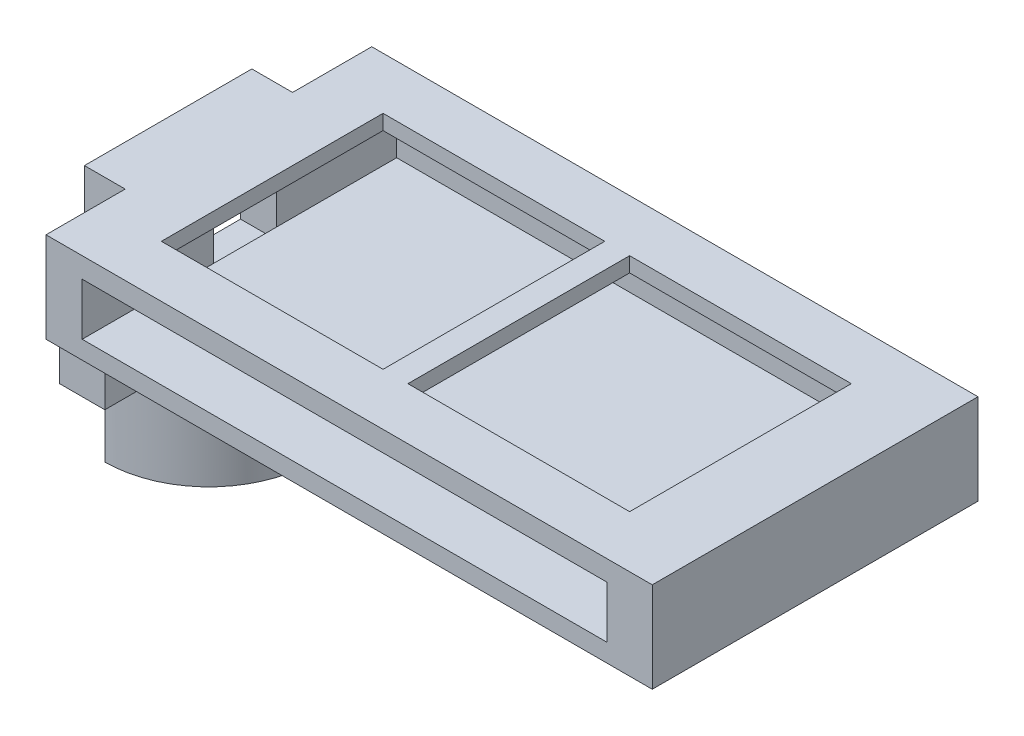
SolidWorks part; units mm, degrees
ref_plane "Front Plane" through (0, 0, 0) normal (0, 0, 1) x (1, 0, 0)
ref_plane "Top Plane" through (0, 0, 0) normal (0, 1, 0) x (1, 0, 0)
ref_plane "Right Plane" through (0, 0, 0) normal (1, 0, 0) x (0, 0, -1)
sketch "Sketch5" plane through (0, 0, 0) normal (0, 1, 0) x (1, 0, 0)
  line L0 (-124, 0) -> (-134, 0)
  line L1 (0, 0) -> (-1.9533, 0)
  line L2 (0, 0) -> (0, 72)
  line L3 (0, 72) -> (-134, 72)
  line L4 (-134, 0) -> (-134, 72)
  line L10 (-124, 0) -> (-1.9533, 0)
  dimension "D1" = 72
  dimension "D2" = 134
extrude "Main Body" add sketch "Sketch5" against normal blind 16 contours L1 L2 L3 L4 region at (-67, 0, -36)
sketch "Sketch8" plane through (0, 0, 0) normal (0, 0, 1) x (1, 0, 0)
  line L0 (-134, -16) -> (-134, 0) construction
  line L1 (0, -16) -> (-134, -16)
  line L2 (0, -16) -> (0, -20)
  line L3 (0, -20) -> (-134, -20)
  line L4 (-134, -16) -> (-134, -20)
  dimension "D1" = 4
extrude "Cover" add sketch "Sketch8" against normal up to surface (72 mm away) up to face at (-67, -8, -72)
sketch "Sketch20" plane through (0, 0, 0) normal (0, 0, 1) x (1, 0, 0)
  line L0 (-134, -20) -> (-134, 0) construction
  line L1 (-10, -4.5) -> (-126, -4.5)
  line L2 (-10, -4.5) -> (-10, -16)
  line L3 (-10, -16) -> (-126, -16)
  line L4 (-126, -4.5) -> (-126, -16)
  line L5 (0, -20) -> (0, 0) construction
  line L7 (-134, -20) -> (0, -20) construction
  dimension "D1" = 8
  dimension "D2" = 10
  dimension "D3" = 11.5
  dimension "D4" = 4
extrude "Crystal Slot" cut sketch "Sketch20" against normal offset from surface (69.5 mm away) 2.5 contours L2 L1 L4 L3 up to face at (-67, -10, -72)
sketch "Sketch9" plane through (-134, 0, 0) normal (-1, 0, 0) x (0, 0, 1)
  line L3 (-29, -4.5) -> (-43, -4.5)
  line L4 (-43, -18.5) -> (-43, -4.5)
  line L5 (-72, -20) -> (-72, 0) construction
  line L6 (-69.5, -4.5) -> (0, -4.5) construction
  line L7 (-29, -4.5) -> (-29, -18.5)
  line L8 (-29, -18.5) -> (-43, -18.5)
  dimension "D1" = 14
  dimension "D2" = 14
  dimension "D3" = 29
  dimension "D4" = 0
extrude "SiPM Window" cut sketch "Sketch9" against normal up to surface (8 mm away) up to face at (-126, -10.25, -34.75)
sketch "Sketch10" plane through (0, -20, 0) normal (0, -1, 0) x (1, 0, 0)
  line L0 (-134, -72) -> (-134, 0) construction
  line L4 (-134, -72) -> (-134, 0) construction
  line L5 (-134, -72) -> (0, -72) construction
  line L6 (-134, -16) -> (-134, -13)
  line L7 (-134, -56) -> (-134, -59)
  arc A0 (-134, -56) -> (-134, -16) centre (-134, -36) ccw
  arc A1 (-134, -59) -> (-134, -13) centre (-134, -36) ccw
  line M4 (-134, 0) -> (-134, -72)
  line M8 (-134, 0) -> (-134, -72)
  dimension "D2" = 20
  dimension "D1" = 36
  dimension "D3" = 3
  dimension "D4" = 3
extrude "Tube Adapter" add sketch "Sketch10" along normal blind 30 contours A1 A0 M4 M8 region at (-133.4857, -20, -14.5)
sketch "Sketch11" plane through (0, -20, 0) normal (0, -1, 0) x (1, 0, 0)
  line L0 (-134, -59) -> (-134, -69)
  line L5 (-134, -72) -> (-134, -59) construction
  line L6 (-134, -69) -> (-124, -69)
  line L7 (-124, -69) -> (-124, -56.7123)
  arc A0 (-134, -59) -> (-124, -56.7123) centre (-134, -36) ccw
  dimension "D1" = 10
  dimension "D2" = 10
extrude "Right Screw Terminal" add sketch "Sketch11" along normal blind 10
sketch "Sketch12" plane through (-134, 0, 0) normal (-1, 0, 0) x (0, 0, 1)
  line L2 (-69, -30) -> (-69, -20) construction
  line L3 (-59, -30) -> (-69, -30) construction
  circle A0 centre (-64, -25) radius 1.524
  dimension "D3" = 5
  dimension "D1" = 3.048
  dimension "D2" = 5
extrude "Right Screw Hole" cut sketch "Sketch12" against normal up to next
sketch "Sketch13" plane through (0, -20, 0) normal (0, -1, 0) x (-1, 0, 0)
  line L2 (134, 13) -> (134, 3)
  line L3 (134, 3) -> (124, 3)
  line L4 (124, 15.2877) -> (124, 3)
  arc A0 (134, 13) -> (124, 15.2877) centre (134, 36) cw
  dimension "D1" = 10
  dimension "D2" = 10
extrude "Left Screw Terminal" add sketch "Sketch13" along normal blind 10
sketch "Sketch14" plane through (-134, 0, 0) normal (-1, 0, 0) x (0, 0, 1)
  line L0 (-3, -30) -> (-3, -20) construction
  line L1 (-3, -30) -> (-13, -30) construction
  circle A0 centre (-8, -25) radius 1.524
  dimension "D3" = 3.048
  dimension "D1" = 5
  dimension "D2" = 5
extrude "Left Screw Hole" cut sketch "Sketch14" against normal up to next
sketch "Sketch15" plane through (-134, 0, 0) normal (-1, 0, 0) x (0, 0, 1)
  line L0 (-56, -20) -> (-16, -20) construction
  line L1 (-17.5, -20) -> (-54.5, -20)
  line L2 (-17.5, -20) -> (-17.5, 0)
  line L3 (-17.5, 0) -> (-54.5, 0)
  line L4 (-54.5, -20) -> (-54.5, 0)
  line L7 (0, 0) -> (-72, 0) construction
  line L8 (-43, -4.5) -> (-43, -18.5) construction
  dimension "D1" = 37
  dimension "D2" = 11.5
extrude "SiPM Mount" add sketch "Sketch15" along normal blind 9
sketch "Sketch17" plane through (0, -20, 0) normal (0, -1, 0) x (1, 0, 0)
  line L1 (-134, -18) -> (-142.8, -18)
  line L3 (-134, -54) -> (-142.8, -54)
  line L4 (-142.8, -18) -> (-142.8, -54)
  line L8 (-134, -18) -> (-134, -54)
  line L10 (-126, -29) -> (-134, -29) construction
  dimension "D1" = 36
  dimension "D2" = 11
  dimension "D3" = 8.8
extrude "SiPM Slot" cut sketch "Sketch17" against normal offset from surface (17.5 mm away) 2 up to face at (-99, -4.5, -35.375) offset beyond the face yes
ref_plane "Plane1" through (-144, 0, 0) normal (-1, 0, 0) x (0, 0, 1)
sketch "Sketch18" plane through (-144, 0, 0) normal (-1, 0, 0) x (0, 0, 1)
  line L0 (-56, -50) -> (-56, -20) construction
  line L5 (-56, -50) -> (-16, -50) construction
  circle A0 centre (-36, -42.5) radius 1.524
  dimension "D1" = 3.048
  dimension "D2" = 20
  dimension "D3" = 7.5
extrude "Adapter Hole" cut sketch "Sketch18" against normal up to surface (32.9495 mm away) up to face at (-124.4677, -32.5, -36)
sketch "Sketch21" plane through (0, -4.5, 0) normal (0, -1, 0) x (1, 0, 0)
  line L0 (-10, -69.5) -> (-10, 0) construction
  line L1 (-15, -10) -> (-67, -10)
  line L2 (-15, -10) -> (-15, -62)
  line L3 (-15, -62) -> (-67, -62)
  line L4 (-67, -10) -> (-67, -62)
  line L5 (-69.5, -10) -> (-121.5, -10)
  line L6 (-69.5, -10) -> (-69.5, -62)
  line L7 (-69.5, -62) -> (-121.5, -62)
  line L8 (-121.5, -10) -> (-121.5, -62)
  line L9 (-67, -36) -> (-15, -36) construction
  line L10 (0, -36) -> (-143, -36) construction
  line L11 (0, -72) -> (0, 0) construction
  line L12 (-143, -54.5) -> (-143, -17.5) construction
  line L13 (-121.5, -36) -> (-69.5, -36) construction
  dimension "D1" = 5
  dimension "D2" = 52
  dimension "D3" = 52
  dimension "D4" = 52
  dimension "D5" = 2.5
  dimension "D6" = 52
extrude "Filter Slot" cut sketch "Sketch21" against normal blind 1.2
sketch "Sketch24" plane through (0, -3.3, 0) normal (0, -1, 0) x (1, 0, 0)
  line L0 (-121.5, -10) -> (-121.5, -62) construction
  line L1 (-16.5, -11.5) -> (-65.5, -11.5)
  line L2 (-16.5, -11.5) -> (-16.5, -60.5)
  line L3 (-16.5, -60.5) -> (-65.5, -60.5)
  line L4 (-65.5, -11.5) -> (-65.5, -60.5)
  line L5 (-15, -10) -> (-67, -10) construction
  line L7 (-121.5, -62) -> (-69.5, -62) construction
  line L9 (-15, -62) -> (-15, -10) construction
  line L10 (-67, -62) -> (-15, -62) construction
  line L11 (-67, -10) -> (-67, -62) construction
  line L12 (-69.5, -10) -> (-121.5, -10) construction
  line L13 (-120, -11.5) -> (-71, -11.5)
  line L14 (-120, -11.5) -> (-120, -60.5)
  line L15 (-120, -60.5) -> (-71, -60.5)
  line L16 (-71, -11.5) -> (-71, -60.5)
  line L17 (-69.5, -62) -> (-69.5, -10) construction
  dimension "D1" = 1.5
  dimension "D2" = 1.5
  dimension "D3" = 1.5
  dimension "D4" = 1.5
  dimension "D5" = 1.5
  dimension "D6" = 1.5
  dimension "D7" = 1.5
  dimension "D8" = 1.5
extrude "Filter Window" cut sketch "Sketch24" against normal up to surface (3.3 mm away) up to face at (-102.75, 0, -36)
